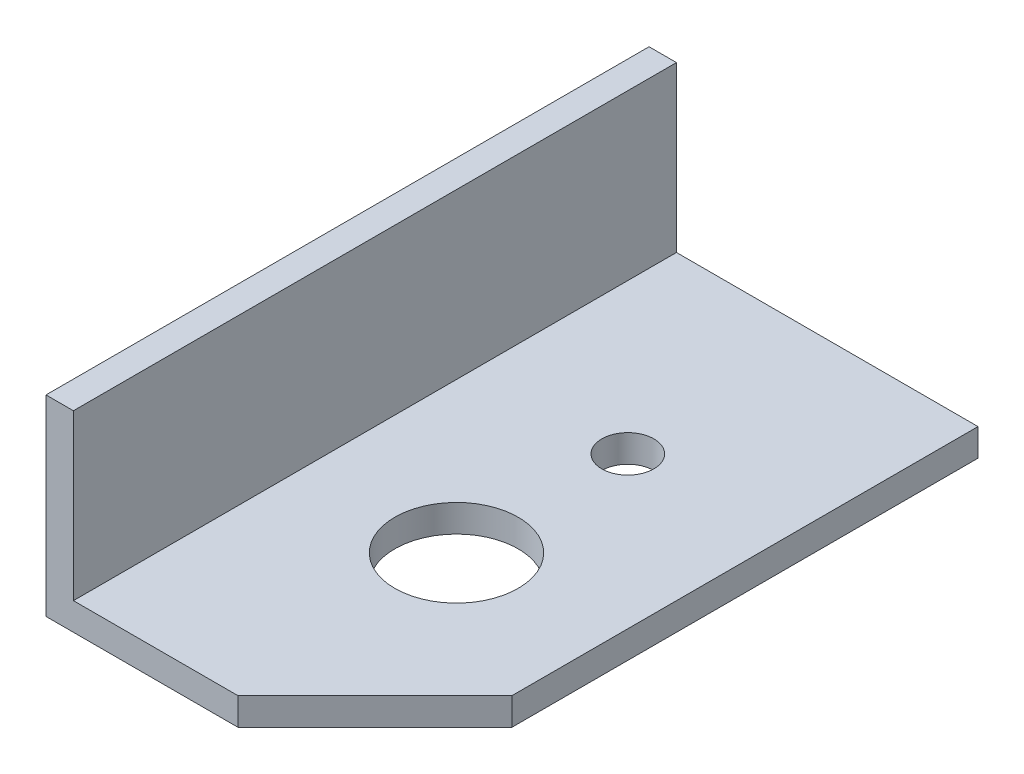
SolidWorks part; units mm, degrees
ref_plane "Спереди" through (0, 0, 0) normal (0, 0, 1) x (1, 0, 0)
ref_plane "Сверху" through (0, 0, 0) normal (0, 1, 0) x (1, 0, 0)
ref_plane "Справа" through (0, 0, 0) normal (1, 0, 0) x (0, 0, -1)
sketch "Эскиз2" plane through (0, 0, 0) normal (0, 0, 1) x (1, 0, 0)
  line L0 (0, 0) -> (0, 14)
  line L1 (0, 0) -> (24, 0)
extrude "Вытянуть-Тонкостенный1" add sketch "Эскиз2" along normal blind 44 thin thin type one direction reverse wall 2
sketch "Эскиз4" plane through (0, 2, 0) normal (0, 1, 0) x (-1, 0, 0)
  circle A0 centre (-12.95, 14.5) radius 1.9
  circle A1 centre (-12.95, 27) radius 4.5
extrude "Вырез-Вытянуть1" cut sketch "Эскиз4" against normal through all
chamfer "Фаска1" distance 10 angle 45 1 edges at (24, 1, 44)
